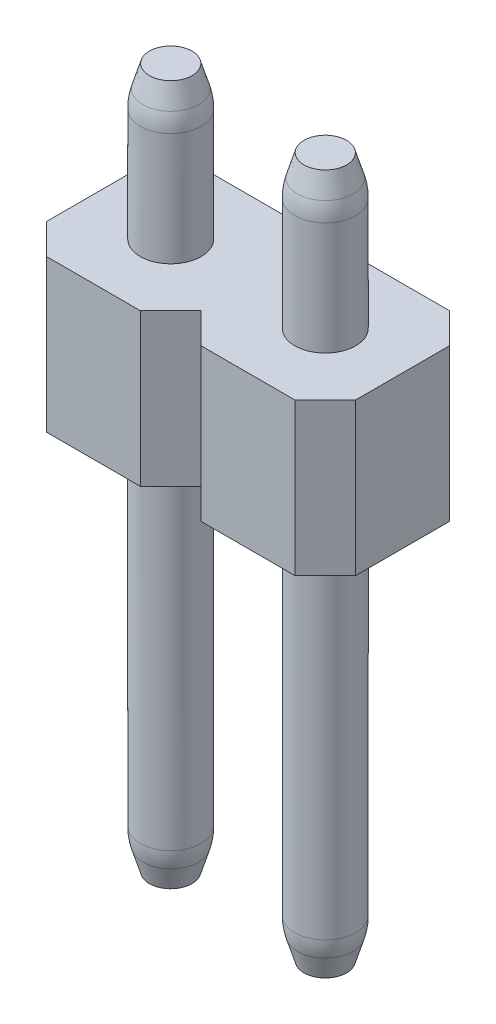
SolidWorks part; units mm, degrees
material "Brass"
ref_plane "Front Plane" through (0, 0, 0) normal (0, 0, 1) x (1, 0, 0)
ref_plane "Top Plane" through (0, 0, 0) normal (0, 1, 0) x (1, 0, 0)
ref_plane "Right Plane" through (0, 0, 0) normal (1, 0, 0) x (0, 0, -1)
sketch "Sketch1" plane through (0, 0, 0) normal (0, 1, 0) x (1, 0, 0)
  line L0 (0, 0) -> (2.54, 0) construction
  circle A0 centre (0, 0) radius 0.5
  circle A1 centre (2.54, 0) radius 0.5
  circle A2 centre (5.08, 0) radius 0.5
  circle A3 centre (7.62, 0) radius 0.5
  circle A4 centre (10.16, 0) radius 0.5
  circle A5 centre (12.7, 0) radius 0.5
  circle A6 centre (15.24, 0) radius 0.5
  circle A7 centre (17.78, 0) radius 0.5
  circle A8 centre (20.32, 0) radius 0.5
  circle A9 centre (22.86, 0) radius 0.5
  circle A10 centre (25.4, 0) radius 0.5
  circle A11 centre (27.94, 0) radius 0.5
  circle A12 centre (30.48, 0) radius 0.5
  circle A13 centre (33.02, 0) radius 0.5
  circle A14 centre (35.56, 0) radius 0.5
  circle A15 centre (38.1, 0) radius 0.5
  dimension "D1" = 1
  dimension "D3" = 2.54
  dimension "D2" = 16
extrude "Boss-Extrude1" add sketch "Sketch1" along normal blind 11.5
ref_plane "Plane1" through (0, 6.5, 0) normal (0, 1, 0) x (1, 0, 0)
sketch "Sketch2" plane through (0, 6.5, 0) normal (0, 1, 0) x (1, 0, 0)
  line L0 (-1.27, 0.77) -> (-0.77, 1.27)
  line L1 (-0.77, -1.27) -> (0.77, -1.27)
  line L2 (-1.27, -0.77) -> (-1.27, 0.77)
  line L3 (-0.77, 1.27) -> (0.77, 1.27)
  line L5 (-1.27, -1.27) -> (1.27, 1.27) construction
  line L6 (-1.27, 1.27) -> (1.27, -1.27) construction
  line L7 (0.77, 1.27) -> (1.27, 0.77)
  line L8 (0.77, -1.27) -> (1.27, -0.77)
  line L9 (-1.27, -0.77) -> (-0.77, -1.27)
  line L10 (1.27, 0.77) -> (1.77, 1.27)
  line L11 (1.77, 1.27) -> (3.31, 1.27)
  line L12 (3.31, 1.27) -> (3.81, 0.77)
  line L14 (3.31, -1.27) -> (3.81, -0.77)
  line L15 (1.77, -1.27) -> (3.31, -1.27)
  line L16 (1.27, -0.77) -> (1.77, -1.27)
  line L17 (3.81, 0.77) -> (4.31, 1.27)
  line L18 (4.31, 1.27) -> (5.85, 1.27)
  line L19 (5.85, 1.27) -> (6.35, 0.77)
  line L20 (6.35, -0.77) -> (6.35, 0.77) construction
  line L21 (5.85, -1.27) -> (6.35, -0.77)
  line L22 (4.31, -1.27) -> (5.85, -1.27)
  line L23 (3.81, -0.77) -> (4.31, -1.27)
  line L24 (6.35, 0.77) -> (6.85, 1.27)
  line L25 (6.85, 1.27) -> (8.39, 1.27)
  line L26 (8.39, 1.27) -> (8.89, 0.77)
  line L27 (8.89, -0.77) -> (8.89, 0.77) construction
  line L28 (8.39, -1.27) -> (8.89, -0.77)
  line L29 (6.85, -1.27) -> (8.39, -1.27)
  line L30 (6.35, -0.77) -> (6.85, -1.27)
  line L31 (8.89, 0.77) -> (9.39, 1.27)
  line L32 (9.39, 1.27) -> (10.93, 1.27)
  line L33 (10.93, 1.27) -> (11.43, 0.77)
  line L34 (11.43, -0.77) -> (11.43, 0.77) construction
  line L35 (10.93, -1.27) -> (11.43, -0.77)
  line L36 (9.39, -1.27) -> (10.93, -1.27)
  line L37 (8.89, -0.77) -> (9.39, -1.27)
  line L38 (11.43, 0.77) -> (11.93, 1.27)
  line L39 (11.93, 1.27) -> (13.47, 1.27)
  line L40 (13.47, 1.27) -> (13.97, 0.77)
  line L41 (13.97, -0.77) -> (13.97, 0.77) construction
  line L42 (13.47, -1.27) -> (13.97, -0.77)
  line L43 (11.93, -1.27) -> (13.47, -1.27)
  line L44 (11.43, -0.77) -> (11.93, -1.27)
  line L45 (13.97, 0.77) -> (14.47, 1.27)
  line L46 (14.47, 1.27) -> (16.01, 1.27)
  line L47 (16.01, 1.27) -> (16.51, 0.77)
  line L48 (16.51, -0.77) -> (16.51, 0.77) construction
  line L49 (16.01, -1.27) -> (16.51, -0.77)
  line L50 (14.47, -1.27) -> (16.01, -1.27)
  line L51 (13.97, -0.77) -> (14.47, -1.27)
  line L52 (16.51, 0.77) -> (17.01, 1.27)
  line L53 (17.01, 1.27) -> (18.55, 1.27)
  line L54 (18.55, 1.27) -> (19.05, 0.77)
  line L55 (19.05, -0.77) -> (19.05, 0.77) construction
  line L56 (18.55, -1.27) -> (19.05, -0.77)
  line L57 (17.01, -1.27) -> (18.55, -1.27)
  line L58 (16.51, -0.77) -> (17.01, -1.27)
  line L59 (19.05, 0.77) -> (19.55, 1.27)
  line L60 (19.55, 1.27) -> (21.09, 1.27)
  line L61 (21.09, 1.27) -> (21.59, 0.77)
  line L62 (21.59, -0.77) -> (21.59, 0.77) construction
  line L63 (21.09, -1.27) -> (21.59, -0.77)
  line L64 (19.55, -1.27) -> (21.09, -1.27)
  line L65 (19.05, -0.77) -> (19.55, -1.27)
  line L66 (21.59, 0.77) -> (22.09, 1.27)
  line L67 (22.09, 1.27) -> (23.63, 1.27)
  line L68 (23.63, 1.27) -> (24.13, 0.77)
  line L69 (24.13, -0.77) -> (24.13, 0.77) construction
  line L70 (23.63, -1.27) -> (24.13, -0.77)
  line L71 (22.09, -1.27) -> (23.63, -1.27)
  line L72 (21.59, -0.77) -> (22.09, -1.27)
  line L73 (24.13, 0.77) -> (24.63, 1.27)
  line L74 (24.63, 1.27) -> (26.17, 1.27)
  line L75 (26.17, 1.27) -> (26.67, 0.77)
  line L76 (26.67, -0.77) -> (26.67, 0.77) construction
  line L77 (26.17, -1.27) -> (26.67, -0.77)
  line L78 (24.63, -1.27) -> (26.17, -1.27)
  line L79 (24.13, -0.77) -> (24.63, -1.27)
  line L80 (26.67, 0.77) -> (27.17, 1.27)
  line L81 (27.17, 1.27) -> (28.71, 1.27)
  line L82 (28.71, 1.27) -> (29.21, 0.77)
  line L83 (29.21, -0.77) -> (29.21, 0.77) construction
  line L84 (28.71, -1.27) -> (29.21, -0.77)
  line L85 (27.17, -1.27) -> (28.71, -1.27)
  line L86 (26.67, -0.77) -> (27.17, -1.27)
  line L87 (29.21, 0.77) -> (29.71, 1.27)
  line L88 (29.71, 1.27) -> (31.25, 1.27)
  line L89 (31.25, 1.27) -> (31.75, 0.77)
  line L90 (31.75, -0.77) -> (31.75, 0.77) construction
  line L91 (31.25, -1.27) -> (31.75, -0.77)
  line L92 (29.71, -1.27) -> (31.25, -1.27)
  line L93 (29.21, -0.77) -> (29.71, -1.27)
  line L94 (31.75, 0.77) -> (32.25, 1.27)
  line L95 (32.25, 1.27) -> (33.79, 1.27)
  line L96 (33.79, 1.27) -> (34.29, 0.77)
  line L97 (34.29, -0.77) -> (34.29, 0.77) construction
  line L98 (33.79, -1.27) -> (34.29, -0.77)
  line L99 (32.25, -1.27) -> (33.79, -1.27)
  line L100 (31.75, -0.77) -> (32.25, -1.27)
  line L101 (34.29, 0.77) -> (34.79, 1.27)
  line L102 (34.79, 1.27) -> (36.33, 1.27)
  line L103 (36.33, 1.27) -> (36.83, 0.77)
  line L104 (36.83, -0.77) -> (36.83, 0.77) construction
  line L105 (36.33, -1.27) -> (36.83, -0.77)
  line L106 (34.79, -1.27) -> (36.33, -1.27)
  line L107 (34.29, -0.77) -> (34.79, -1.27)
  line L108 (36.83, 0.77) -> (37.33, 1.27)
  line L109 (37.33, 1.27) -> (38.87, 1.27)
  line L110 (38.87, 1.27) -> (39.37, 0.77)
  line L111 (39.37, -0.77) -> (39.37, 0.77)
  line L112 (38.87, -1.27) -> (39.37, -0.77)
  line L113 (37.33, -1.27) -> (38.87, -1.27)
  line L114 (36.83, -0.77) -> (37.33, -1.27)
  line L115 (-1.27, 0.77) -> (1.27, 0.77) construction
  point P0 (0, 0)
  dimension "D1" = 2.54
  dimension "D2" = 2.54
  dimension "D4" = 2.54
  dimension "D3" = 16
extrude "Boss-Extrude2" add sketch "Sketch2" along normal blind 2.5
chamfer "Chamfer1" distance 0.5 distance2 0.15 16 edges at (15.24, 11.5, 0.5) (12.7, 11.5, 0.5) (10.16, 11.5, 0.5) (7.62, 11.5, 0.5) (5.08, 11.5, 0.5) (2.54, 11.5, 0.5) (0, 11.5, 0.5) (38.1, 11.5, 0.5) (35.56, 11.5, 0.5) (33.02, 11.5, 0.5) (30.48, 11.5, 0.5) (27.94, 11.5, 0.5) (25.4, 11.5, 0.5) (22.86, 11.5, 0.5) (20.32, 11.5, 0.5) (17.78, 11.5, 0.5) first distance on face at (15.24, 11.5, 0.5) first distance on face at (12.7, 11.5, 0.5) first distance on face at (10.16, 11.5, 0.5) first distance on face at (7.62, 11.5, 0.5) first distance on face at (5.08, 11.5, 0.5) first distance on face at (2.54, 11.5, 0.5) first distance on face at (0, 11.5, 0.5) first distance on face at (38.1, 11.5, 0.5) first distance on face at (35.56, 11.5, 0.5) first distance on face at (33.02, 11.5, 0.5) first distance on face at (30.48, 11.5, 0.5) first distance on face at (27.94, 11.5, 0.5) first distance on face at (25.4, 11.5, 0.5) first distance on face at (22.86, 11.5, 0.5) first distance on face at (20.32, 11.5, 0.5) first distance on face at (17.78, 11.5, 0.5)
fillet "Fillet1" radius 1 16 edges at (38.1, 11, 0.5) (35.56, 11, 0.5) (33.02, 11, 0.5) (30.48, 11, 0.5) (27.94, 11, 0.5) (25.4, 11, 0.5) (22.86, 11, 0.5) (20.32, 11, 0.5) (17.78, 11, 0.5) (15.24, 11, 0.5) (12.7, 11, 0.5) (10.16, 11, 0.5) (7.62, 11, 0.5) (5.08, 11, 0.5) (2.54, 11, 0.5) (0, 11, 0.5)
chamfer "Chamfer2" distance 0.15 distance2 0.5 16 edges at (10.16, 0, 0.5) (17.78, 0, 0.5) (22.86, 0, 0.5) (27.94, 0, 0.5) (30.48, 0, 0.5) (0, 0, 0.5) (2.54, 0, 0.5) (5.08, 0, 0.5) (7.62, 0, 0.5) (12.7, 0, 0.5) (15.24, 0, 0.5) (20.32, 0, 0.5) (25.4, 0, 0.5) (33.02, 0, 0.5) (35.56, 0, 0.5) (38.1, 0, 0.5) first distance on face at (10.16, 0, 0.5) first distance on face at (17.78, 0, 0.5) first distance on face at (22.86, 0, 0.5) first distance on face at (27.94, 0, 0.5) first distance on face at (30.48, 0, 0.5) first distance on face at (0, 0, 0.5) first distance on face at (2.54, 0, 0.5) first distance on face at (5.08, 0, 0.5) first distance on face at (7.62, 0, 0.5) first distance on face at (12.7, 0, 0.5) first distance on face at (15.24, 0, 0.5) first distance on face at (20.32, 0, 0.5) first distance on face at (25.4, 0, 0.5) first distance on face at (33.02, 0, 0.5) first distance on face at (35.56, 0, 0.5) first distance on face at (38.1, 0, 0.5)
fillet "Fillet2" radius 1 16 edges at (30.48, 0.5, 0.5) (33.02, 0.5, 0.5) (35.56, 0.5, 0.5) (38.1, 0.5, 0.5) (27.94, 0.5, 0.5) (25.4, 0.5, 0.5) (22.86, 0.5, 0.5) (20.32, 0.5, 0.5) (17.78, 0.5, 0.5) (15.24, 0.5, 0.5) (12.7, 0.5, 0.5) (10.16, 0.5, 0.5) (7.62, 0.5, 0.5) (5.08, 0.5, 0.5) (2.54, 0.5, 0.5) (0, 0.5, 0.5)
sketch "Sketch3" plane through (0, 0, 1.27) normal (0, 0, 1) x (1, 0, 0)
  line L0 (29.21, 9) -> (29.21, 6.5) construction
  line L1 (29.21, 9) -> (29.21, 6.5)
  line L2 (29.21, 9) -> (29.21, 12.0063)
  line L3 (29.21, 12.0063) -> (41.7324, 12.0063)
  line L4 (41.7324, 12.0063) -> (41.7324, -0.9046)
  line L5 (41.7324, -0.9046) -> (29.21, -0.9046)
  line L6 (29.21, -0.9046) -> (29.21, 6.5)
extrude "Cut-Extrude1" cut sketch "Sketch3" against normal through all
sketch "Sketch4" plane through (0, 0, 1.27) normal (0, 0, 1) x (1, 0, 0)
  line L0 (16.51, 9) -> (16.51, 6.5) construction
  line L1 (16.51, 9) -> (16.51, 6.5)
  line L2 (16.51, 9) -> (16.51, 12.1306)
  line L3 (16.51, 12.1306) -> (30.5961, 12.1306)
  line L4 (30.5961, 12.1306) -> (30.5961, -1.1631)
  line L5 (30.5961, -1.1631) -> (16.51, -1.1631)
  line L6 (16.51, -1.1631) -> (16.51, 6.5)
extrude "Cut-Extrude2" cut sketch "Sketch4" against normal through all
sketch "Sketch5" plane through (0, 0, 1.27) normal (0, 0, 1) x (1, 0, 0)
  line L0 (3.81, 9) -> (3.81, 6.5) construction
  line L1 (3.81, 11.5) -> (3.81, 0)
  line L2 (3.81, 11.5) -> (16.51, 11.5)
  line L3 (16.51, 11.5) -> (16.51, 0)
  line L4 (16.51, 0) -> (3.81, 0)
extrude "Cut-Extrude3" cut sketch "Sketch5" against normal through all both and the other way through all
